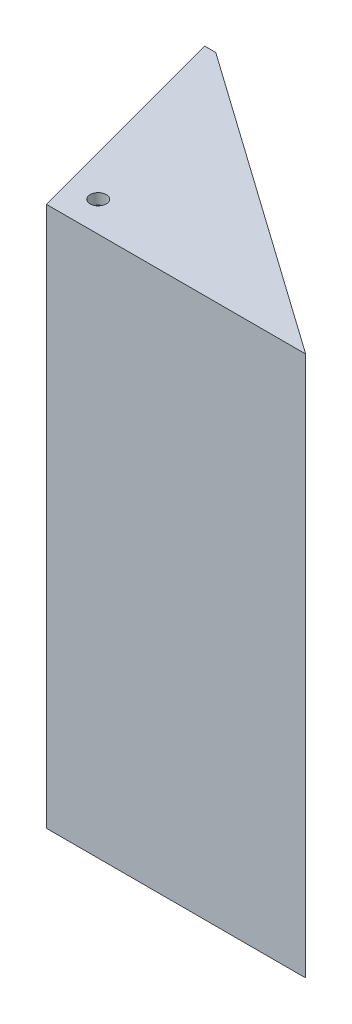
SolidWorks part; units mm, degrees
ref_plane "Front Plane" through (0, 0, 0) normal (0, 0, 1) x (1, 0, 0)
ref_plane "Top Plane" through (0, 0, 0) normal (0, 1, 0) x (1, 0, 0)
ref_plane "Right Plane" through (0, 0, 0) normal (1, 0, 0) x (0, 0, -1)
sketch "Sketch1" plane through (0, 0, 0) normal (0, 1, 0) x (1, 0, 0)
  line L0 (0, 0) -> (76.2, 0)
  line L5 (76.2, 0) -> (76.2, 63.5)
  line L6 (76.2, 63.5) -> (-17.0148, 63.5)
  line L7 (-17.0148, 63.5) -> (0, 0)
  dimension "D1" = 75
  dimension "D2" = 63.5
  dimension "D3" = 76.2
extrude "Boss-Extrude1" add sketch "Sketch1" along normal blind 3.175 contours L7 L0 L5 L6
sketch "Sketch2" plane through (0, 3.175, 0) normal (0, 1, 0) x (1, 0, 0)
  line L2 (76.2, 0) -> (0, 0)
  line L3 (0, 0) -> (-17.0148, 63.5)
  line L6 (76.2, 3.175) -> (2.4363, 3.175)
  line L7 (2.4363, 3.175) -> (-13.7278, 63.5)
  line L8 (76.2, 0) -> (76.2, 63.5) construction
  line L9 (76.2, 63.5) -> (-17.0148, 63.5) construction
  line L10 (76.2, 0) -> (76.2, 3.175)
  line L11 (-17.0148, 63.5) -> (-13.7278, 63.5)
  dimension "D1" = 3.175
  dimension "D4" = 3.175
extrude "Boss-Extrude3" add sketch "Sketch2" along normal blind 152.4
sketch "Sketch3" plane through (0, 155.575, 0) normal (0, 1, 0) x (1, 0, 0)
  line L0 (-17.0148, 63.5) -> (0, 0)
  line L1 (0, 0) -> (76.2, 0)
  line L2 (76.2, 0) -> (76.2, 63.5)
  line L3 (76.2, 63.5) -> (-17.0148, 63.5)
extrude "Boss-Extrude4" add sketch "Sketch3" along normal blind 3.175
chamfer "Chamfer1" distance 3.175 angle 75 1 edges at (76.2, 79.375, -3.175) first distance on face at (76.2, 79.375, -32.5438)
sketch "Sketch4" plane through (0, 0, 0) normal (0, -1, 0) x (1, 0, 0)
  line L1 (76.2, 0) -> (76.2, -63.5) construction
  line L2 (0, 0) -> (76.2, 0) construction
  circle A0 centre (6.35, -8.89) radius 2.3813
  dimension "D1" = 4.7625
  dimension "D2" = 8.89
  dimension "D3" = 69.85
extrude "Cut-Extrude1" cut sketch "Sketch4" against normal blind 158.75
sketch "Sketch6" plane through (0, 158.75, 0) normal (0, 1, 0) x (1, 0, 0)
  line L0 (-13.7278, 63.5) -> (76.2, 0)
  line L1 (76.2, 0) -> (76.2, 63.5)
  line L6 (-13.7278, 63.5) -> (76.2, 63.5)
  point P2 (-13.7278, 63.5)
  point P4 (-13.8348, 63.5)
  point P7 (-13.7278, 63.5)
  point P10 (-13.7278, 63.5)
  point P11 (0, 0)
  point P12 (0, 0)
  point P13 (0, 0)
  point P14 (-13.7312, 63.5)
extrude "Cut-Extrude2" cut sketch "Sketch6" against normal blind 254
sketch "Sketch7" plane through (3.0668, 0, -0.8218) normal (0.9659, 0, -0.2588) x (-0.2588, 0, -0.9659)
  line L0 (-19.722, 0) -> (64.8893, 0) construction
  line L2 (64.8893, 155.575) -> (64.8893, 3.175) construction
  circle A0 centre (61.0793, 38.1) radius 1.5875
  dimension "D1" = 3.175
  dimension "D2" = 38.1
  dimension "D3" = 3.81
extrude "Cut-Extrude3" cut sketch "Sketch7" against normal blind 7.62 contours A0
